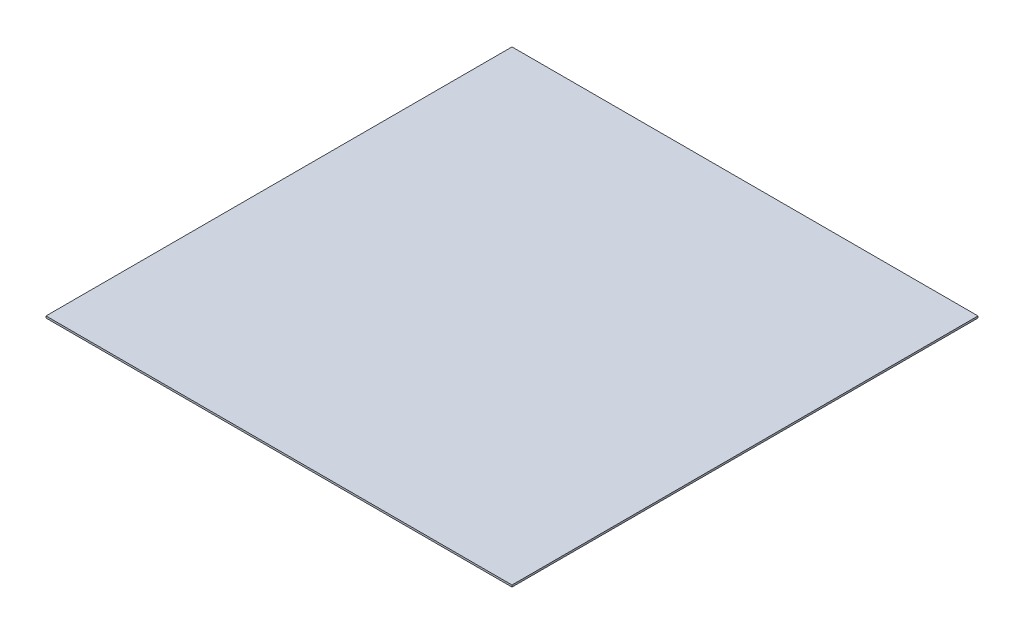
SolidWorks part; units mm, degrees
material "ABS"
ref_plane "FRONT" through (0, 0, 0) normal (0, 0, 1) x (1, 0, 0)
ref_plane "TOP" through (0, 0, 0) normal (0, 1, 0) x (1, 0, 0)
ref_plane "RIGHT" through (0, 0, 0) normal (1, 0, 0) x (0, 0, -1)
ref_axis "Axis1" through (-80.9, 0, 0) along (1, 0, 0)
ref_axis "Axis2" through (0, 0, -80.9) along (0, 0, 1)
ref_axis "Axis3" through (0, 50, 0) along (0, -1, 0)
sketch "Sketch1" plane through (0, 0, 0) normal (0, 1, 0) x (1, 0, 0)
  line L1 (-125, -125) -> (125, -125)
  line L2 (-125, -125) -> (-125, 125)
  line L3 (-125, 125) -> (125, 125)
  line L4 (125, -125) -> (125, 125)
  line L5 (-125, -125) -> (125, 125) construction
  line L6 (-125, 125) -> (125, -125) construction
  point P0 (0, 0)
  dimension "D1" = 250
extrude "Boss-Extrude1" add sketch "Sketch1" along normal blind 1
